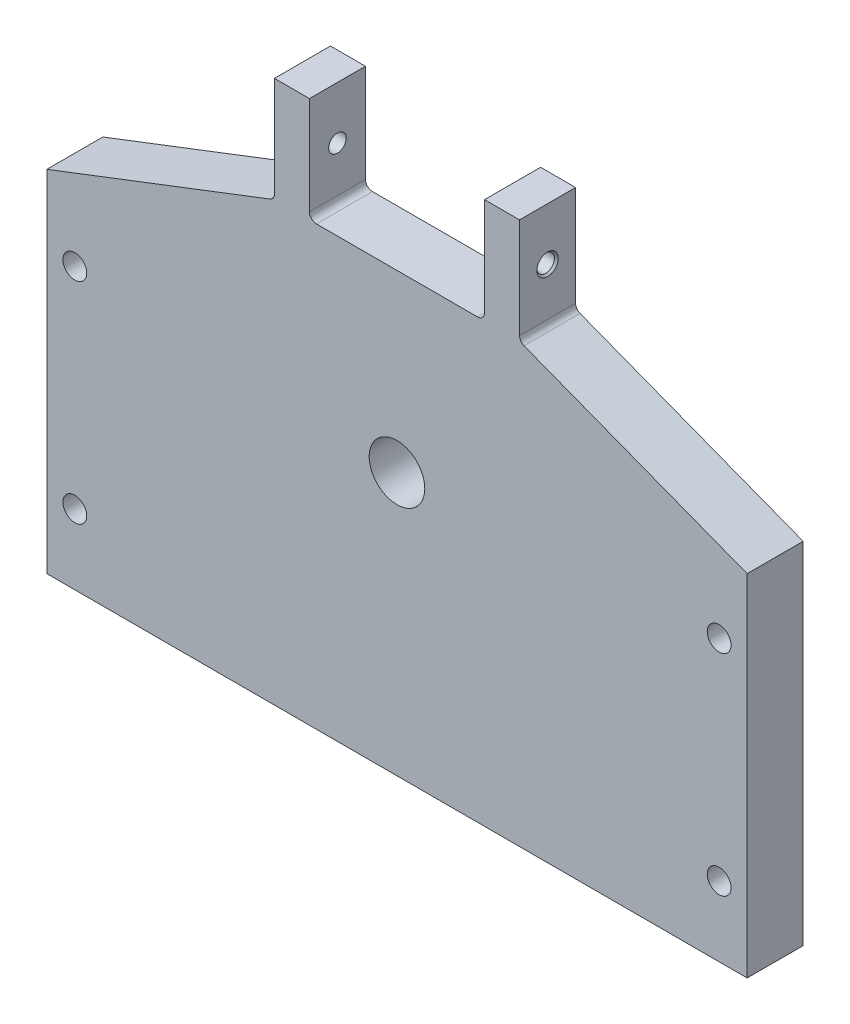
SolidWorks part; units mm, degrees
material "5052-O"
ref_plane "정면" through (0, 0, 0) normal (0, 0, 1) x (1, 0, 0)
ref_plane "윗면" through (0, 0, 0) normal (0, 1, 0) x (1, 0, 0)
ref_plane "우측면" through (0, 0, 0) normal (1, 0, 0) x (0, 0, -1)
sketch "스케치1" plane through (0, 0, 0) normal (0, 0, 1) x (1, 0, 0)
  line L0 (-17.5, 52.5) -> (-17.5, 37.5)
  line L1 (-50, 25) -> (50, 25)
  line L2 (-50, 25) -> (-50, -25)
  line L3 (-50, -25) -> (50, -25)
  line L4 (50, 25) -> (50, -25)
  line L5 (-50, 25) -> (50, -25) construction
  line L6 (-50, -25) -> (50, 25) construction
  line L7 (-17.5, 52.5) -> (-12.5, 52.5)
  line L8 (-12.5, 52.5) -> (-12.5, 37.5)
  line L9 (-12.5, 37.5) -> (12.5, 37.5)
  line L14 (12.5, 37.5) -> (12.5, 52.5)
  line L15 (12.5, 52.5) -> (17.5, 52.5)
  line L16 (-17.5, 37.5) -> (-50, 25)
  line L17 (17.5, 52.5) -> (17.5, 37.5)
  line L18 (17.5, 37.5) -> (50, 25)
  point P0 (0, 0)
  point P12 (-17.5, 45)
  point P19 (0, 12.5)
  dimension "D3" = 37.5
  dimension "D4" = 15
  dimension "D1" = 100
  dimension "D2" = 50
  dimension "D5" = 5
  dimension "D6" = 35
  dimension "D7" = 32.5
extrude "보스-돌출1" add sketch "스케치1" along normal blind 8 contours L1 | L1 | L1 | L1 L2 L3 | L3 L4 L1 | L1 region at (0, 32.4738, 0) region at (0, 0, 0)
hole_wizard "3/8-16 나사 구멍1" positions "스케치2" profile "스케치3" tap size "3/8-16" standard "Ansi Inch" end condition up to next
sketch "스케치2" plane through (0, 0, 8) normal (0, 0, 1) x (1, 0, 0)
  line L0 (-50, -25) -> (50, -25) construction
  point P0 (0, 12.5)
  point P6 (0, -25)
  dimension "D1" = 37.5
sketch "스케치3" plane through (0, 12.5, 8) normal (1, 0, 0) x (0, -1, 0)
  line L0 (0, 0) -> (0, 8)
  line L1 (0, 8) -> (3.9687, 8)
  line L2 (3.9687, 8) -> (3.9687, 0)
  line L5 (3.9687, 0) -> (0, 0)
  line L11 (0, -6.35) -> (0, 107.95) construction
  dimension "관통 탭 드릴 지름" = 7.9375
  dimension "관통 탭 드릴 깊이" = 8
cosmetic thread "구멍 나사산1" parameters "D2"=9.525
hole_wizard "M3 접시 머리 나사용 카운터싱크1" positions "스케치6" profile "스케치7" countersink size "M3" standard "ISO" end condition up to next
sketch "스케치6" plane through (0, 0, 0) normal (0, 0, -1) x (-1, 0, 0)
  line L0 (46, 15) -> (46, -15)
  line L2 (50, 25) -> (50, -25) construction
  point P0 (46, 15)
  point P2 (46, -15)
  point P4 (116.5714, 200.8291)
  point P10 (46, 0)
  point P13 (50, 0)
  dimension "D1" = 30
  dimension "D2" = 4
sketch "스케치7" plane through (-46, 15, 0) normal (1, 0, 0) x (0, 1, 0)
  line L0 (0, 0) -> (0, 8)
  line L1 (0, 8) -> (1.7, 8)
  line L2 (1.7, 8) -> (1.7, 1.45)
  line L3 (1.7, 1.45) -> (3.15, 0)
  line L5 (3.15, 0) -> (0, 0)
  line L6 (-1.7, 1.45) -> (-3.15, 0) construction
  line L11 (0, -6.35) -> (0, 107.95) construction
  dimension "관통 구멍 지름" = 3.4
  dimension "관통 구멍 깊이" = 8
  dimension "표면 카운터싱크 지름" = 6.3
  dimension "표면 카운터싱크 각도" = 90
mirror "대칭 복사2" about plane through (0, 0, 0) normal (1, 0, 0) of "M3 접시 머리 나사용 카운터싱크1"
hole_wizard "M3 나사 구멍1" positions "스케치8" profile "스케치9" tap size "M3" standard "ISO" end condition up to next
sketch "스케치8" plane through (-17.5, 0, 0) normal (-1, 0, 0) x (0, 0, 1)
  line L0 (8, 37.5) -> (0, 37.5) construction
  line L1 (8, 52.5) -> (8, 37.5) construction
  point P0 (4, 45)
  point P6 (4, 37.5)
  point P9 (8, 45)
sketch "스케치9" plane through (-17.5, 45, 4) normal (0, 1, 0) x (0, 0, 1)
  line L0 (0, 0) -> (0, 5)
  line L1 (0, 5) -> (1.25, 5)
  line L2 (1.25, 5) -> (1.25, 0.275)
  line L3 (1.25, 0.275) -> (1.525, 0)
  line L5 (1.525, 0) -> (0, 0)
  line L6 (-1.25, 0.275) -> (-1.525, 0) construction
  line L11 (0, -6.35) -> (0, 107.95) construction
  dimension "관통 탭 드릴 지름" = 2.5
  dimension "관통 탭 드릴 깊이" = 5
  dimension "표면 카운터싱크 지름" = 3.05
  dimension "표면 카운터싱크 각도" = 90
cosmetic thread "구멍 나사산2" parameters "D2"=3
mirror "대칭 복사3" about plane through (0, 0, 0) normal (1, 0, 0) of "M3 나사 구멍1"
cosmetic thread "구멍 나사산3" parameters "D2"=3
fillet "필렛1" radius 1 4 edges at (17.5, 37.5, 4) (-17.5, 37.5, 4) (-12.5, 37.5, 4) (12.5, 37.5, 4)
